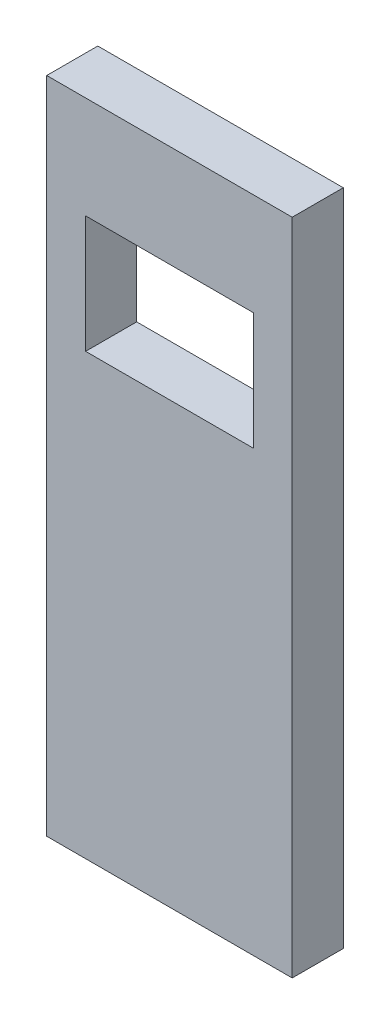
SolidWorks part; units mm, degrees
ref_plane "Front Plane" through (0, 0, 0) normal (0, 0, 1) x (1, 0, 0)
ref_plane "Top Plane" through (0, 0, 0) normal (0, 1, 0) x (1, 0, 0)
ref_plane "Right Plane" through (0, 0, 0) normal (1, 0, 0) x (0, 0, -1)
sketch "Sketch1" plane through (0, 0, 0) normal (0, 0, 1) x (1, 0, 0)
  line L0 (0, 67.1) -> (0, 44.75)
  line L1 (0, 67.1) -> (25, 67.1)
  line L2 (0, 44.75) -> (0, 39.55)
  line L3 (25, 0) -> (0, 0)
  line L4 (3.96, 56.7) -> (21.04, 56.7)
  line L5 (3.96, 44.75) -> (21.04, 44.75)
  line L6 (3.96, 56.7) -> (3.96, 44.75)
  line L7 (21.04, 56.7) -> (21.04, 44.75)
  line L8 (0, 44.75) -> (25, 44.75) construction
  line L9 (0, 39.55) -> (25, 39.55) construction
  line L10 (0, 39.55) -> (0, 27.6)
  line L11 (0, 27.6) -> (0, 22.4)
  line L12 (25, 44.75) -> (25, 39.55)
  line L13 (25, 67.1) -> (25, 44.75)
  line L14 (0, 22.4) -> (0, 0)
  line L15 (25, 39.55) -> (25, 27.6)
  line L16 (25, 27.6) -> (25, 22.4)
  line L17 (25, 22.4) -> (25, 0)
  line L18 (0, 27.6) -> (25, 27.6) construction
  line L19 (25, 22.4) -> (0, 22.4) construction
  line L20 (12.5, -0.0005) -> (12.5, 4.0956) construction
  point P18 (12.5, 44.75)
  point P20 (12.5, 56.7)
  point P21 (12.5, 67.1)
  dimension "D1" = 10.4
  dimension "D2" = 11.95
  dimension "D3" = 5.2
  dimension "D4" = 25
  dimension "D5" = 11.95
  dimension "D6" = 17.08
  dimension "D7" = 22.4
extrude "Boss-Extrude1" add sketch "Sketch1" along normal mid plane 5.2
